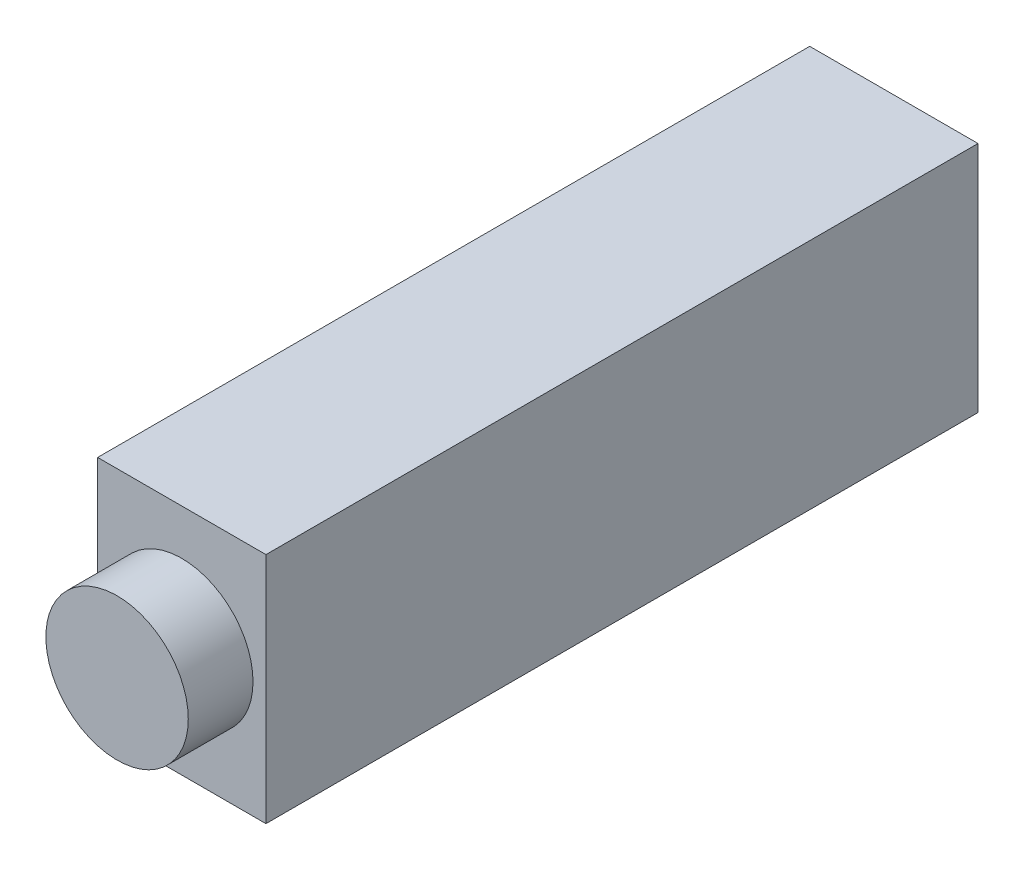
SolidWorks part; units mm, degrees
ref_plane "Front Plane" through (0, 0, 0) normal (0, 0, 1) x (1, 0, 0)
ref_plane "Top Plane" through (0, 0, 0) normal (0, 1, 0) x (1, 0, 0)
ref_plane "Right Plane" through (0, 0, 0) normal (1, 0, 0) x (0, 0, -1)
sketch "Sketch1" plane through (0, 0, 0) normal (0, 0, 1) x (1, 0, 0)
  circle A0 centre (0, 0) radius 11
  dimension "D1" = 22
extrude "Boss-Extrude1" add sketch "Sketch1" along normal blind 10
sketch "Sketch2" plane through (0, 0, 0) normal (0, 0, -1) x (-1, 0, 0)
  circle A0 centre (0, 0) radius 20
  dimension "D1" = 40
sketch "Sketch3" plane through (0, 0, 0) normal (0, 0, -1) x (-1, 0, 0)
  line L1 (13, 18) -> (-13, 18)
  line L2 (13, 18) -> (13, -18)
  line L3 (13, -18) -> (-13, -18)
  line L4 (-13, 18) -> (-13, -18)
  line L5 (13, 18) -> (-13, -18) construction
  line L6 (13, -18) -> (-13, 18) construction
  point P0 (0, 0)
  dimension "D1" = 26
  dimension "D2" = 36
extrude "Boss-Extrude2" add sketch "Sketch3" along normal blind 110
sketch "Sketch4" plane through (13, 0, 0) normal (1, 0, 0) x (0, 0, -1)
  line L0 (110, -18) -> (87.5, -18) construction
  line L1 (110, -18) -> (0, -18) construction
  line L2 (87.5, -18) -> (87.5, -5.5) construction
  circle A0 centre (87.5, -5.5) radius 7.125
  dimension "D3" = 14.25
  dimension "D1" = 22.5
  dimension "D2" = 12.5
